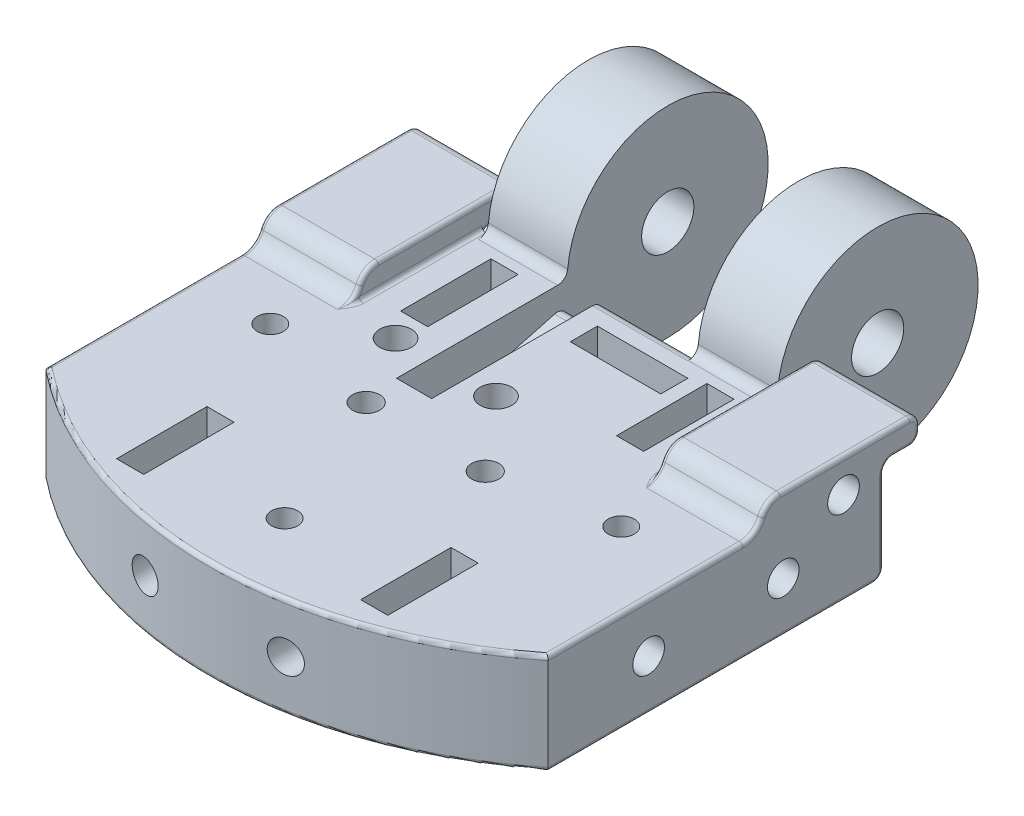
SolidWorks part; units mm, degrees
ref_plane "Front Plane" through (0, 0, 0) normal (0, 0, 1) x (1, 0, 0)
ref_plane "Top Plane" through (0, 0, 0) normal (0, 1, 0) x (1, 0, 0)
ref_plane "Right Plane" through (0, 0, 0) normal (1, 0, 0) x (0, 0, -1)
sketch "Sketch1" plane through (0, 0, 0) normal (0, 1, 0) x (1, 0, 0)
  line L1 (-31.75, 0) -> (31.75, 0)
  line L2 (-31.75, 0) -> (-31.75, -42.418)
  line L4 (31.75, 0) -> (31.75, -42.418)
  arc A0 (-31.75, -42.418) -> (31.75, -42.418) centre (0, -2.7623) ccw
  point P4 (0, 0)
  dimension "D3" = 50.8
  dimension "D1" = 63.5
  dimension "D2" = 42.418
extrude "Boss-Extrude1" add sketch "Sketch1" along normal blind 12.7
ref_plane "Plane1" through (-18.288, 0, 0) normal (-1, 0, 0) x (0, 0, 1)
sketch "Sketch2" plane through (-18.288, 0, 0) normal (-1, 0, 0) x (0, 0, 1)
  line L7 (0, 0) -> (0, 17.5687) construction
  line L9 (0, 0) -> (-12.7, 0)
  line L10 (0, 0) -> (0, 12.7)
  arc A2 (0, 12.7) -> (-12.7, 0) centre (-12.7, 12.7) ccw
  point P2 (-12.7, 0)
  point P3 (0, 12.7)
  dimension "D1" = 25.4
  dimension "D2" = 17.5687
extrude "Boss-Extrude2" add sketch "Sketch2" against normal blind 10.033
mirror "Mirror1" about plane through (0, 0, 0) normal (1, 0, 0) of "Boss-Extrude2"
sketch "Sketch5" plane through (-18.288, 0, 0) normal (-1, 0, 0) x (0, 0, 1)
  circle A0 centre (-12.7, 12.7) radius 3.302
  point P3 (-12.7, 12.7)
  dimension "D1" = 6.604
extrude "Cut-Extrude2" cut sketch "Sketch5" against normal through all
sketch "Sketch13" plane through (0, 12.7, 0) normal (0, 1, 0) x (1, 0, 0)
  line L0 (-31.75, 0) -> (-31.75, -42.418) construction
  line L1 (8.255, 0) -> (-8.255, 0) construction
  circle A0 centre (-12.7, -17.272) radius 2
  circle A1 centre (0, -17.272) radius 2
  dimension "D1" = 4
  dimension "D2" = 19.05
  dimension "D3" = 12.7
  dimension "D4" = 17.272
extrude "Cut-Extrude9" cut sketch "Sketch13" against normal through all
sketch "Sketch17" plane through (0, 12.7, 0) normal (0, 1, 0) x (1, 0, 0)
  line L0 (-31.75, -15.24) -> (-19.05, -15.24)
  line L2 (-31.75, 0) -> (-31.75, 4.572)
  line L3 (-31.75, 4.572) -> (-19.05, 4.572)
  line L4 (-19.05, 0.127) -> (-19.05, 4.572)
  line L7 (-31.75, 0) -> (-31.75, -42.418)
  line L8 (31.75, -42.418) -> (31.75, 0)
  line L9 (31.75, 0) -> (18.288, 0)
  line L10 (18.288, 0) -> (8.255, 0)
  line L11 (8.255, 0) -> (-8.255, 0)
  line L12 (-8.255, 0) -> (-18.288, 0)
  line L13 (-18.288, 0) -> (-31.75, 0)
  line L14 (-31.75, 0) -> (-31.75, -15.24)
  line L22 (-18.288, 0) -> (-31.75, 0) construction
  line L27 (0, 0) -> (0, -53.5623) construction
  line L28 (-19.05, 0.127) -> (-19.05, -15.24)
  line L30 (8.255, 0) -> (-8.255, 0) construction
  line L31 (31.75, -15.24) -> (19.05, -15.24)
  line L32 (19.05, 0.127) -> (19.05, -15.24)
  line L33 (19.05, 0.127) -> (19.05, 4.572)
  line L34 (31.75, 4.572) -> (19.05, 4.572)
  line L35 (31.75, 0) -> (31.75, -15.24)
  line L36 (31.75, 0) -> (31.75, 4.572)
  arc A0 (-31.75, -42.418) -> (31.75, -42.418) centre (0, -2.7623) ccw construction
  arc A1 (-31.75, -42.418) -> (31.75, -42.418) centre (0, -2.7623) ccw
  point P22 (-0.7383, -2.54)
  dimension "D2" = 12.7
  dimension "D3" = 4.572
  dimension "D4" = 15.24
  dimension "D1" = 0
extrude "Boss-Extrude9" add sketch "Sketch17" along normal blind 3.175
ref_plane "Plane2" through (-3.81, 0, 0) normal (1, 0, 0) x (0, 0, -1)
sketch "Sketch19" plane through (-3.81, 0, 0) normal (1, 0, 0) x (0, 0, -1)
  line L1 (-21.59, 4.375) -> (-21.59, 12.7)
  line L2 (-15.24, 15.875) -> (4.572, 15.875) construction
  line L3 (-21.59, 12.7) -> (0, 12.7)
  line L4 (-21.59, 4.375) -> (0, 10.16)
  line L5 (0, 0) -> (0, 12.7) construction
  line L6 (0, 10.16) -> (0, 12.7)
  dimension "D1" = 2.54
  dimension "D2" = 75
  dimension "D3" = 21.59
  dimension "D4" = 3.175
extrude "Cut-Extrude12" cut sketch "Sketch19" against normal blind 4.445
sketch "Sketch23" plane through (0, 0, 0) normal (0, -1, 0) x (-1, 0, 0)
  line L0 (31.75, 0) -> (31.75, -42.418) construction
  line L1 (-31.75, 0) -> (-31.75, -42.418) construction
  line L2 (31.75, -21.209) -> (-31.75, -21.209) construction
  line L3 (23.1652, -1.4218) -> (27.6348, -1.4218)
  line L4 (0, 0) -> (0, -53.5623) construction
  line L5 (-25.4, -5.842) -> (-25.4, -41.402) construction
  line L6 (-21.59, -41.402) -> (-25.4, -41.402) construction
  line L7 (-23.1652, -1.4218) -> (-27.6348, -1.4218)
  arc A0 (23.1652, -1.4218) -> (27.6348, -1.4218) centre (25.4, -5.842) ccw
  arc A1 (-31.75, -42.418) -> (31.75, -42.418) centre (0, -2.7623) ccw construction
  circle A3 centre (21.59, -41.402) radius 4.953
  circle A5 centre (-21.59, -41.402) radius 4.953
  circle A6 centre (0, -22.3203) radius 12.7
  arc A7 (-23.1652, -1.4218) -> (-27.6348, -1.4218) centre (-25.4, -5.842) cw
  point P24 (-25.4, -23.622)
  dimension "D1" = 9.906
  dimension "D4" = 9.906
  dimension "D3" = 35.56
  dimension "D7" = 25.4
  dimension "D8" = 31.242
  dimension "D2" = 50.8
  dimension "D5" = 10.16
  dimension "D6" = 1.016
extrude "Cut-Extrude13" cut sketch "Sketch23" against normal blind 0.0254
sketch "Sketch28" plane through (0, 0, 0) normal (0, -1, 0) x (1, 0, 0)
  line L0 (25.4, 5.842) -> (-25.4, 5.842) construction
  line L1 (31.75, 42.418) -> (31.75, 0) construction
  line L2 (11.9062, 49.7523) -> (-11.9063, 49.7523) construction
  line L3 (11.9062, 49.7523) -> (11.9062, 38.2429) construction
  line L4 (11.9062, 38.2429) -> (-11.9063, 38.2429) construction
  line L5 (-11.9063, 49.7523) -> (-11.9063, 38.2429) construction
  line L6 (11.9062, 49.7523) -> (-11.9063, 38.2429) construction
  line L7 (11.9062, 38.2429) -> (-11.9063, 49.7523) construction
  line L8 (27.94, 35.5283) -> (16.4306, 35.5283) construction
  line L9 (27.94, 35.5283) -> (27.94, 11.7158) construction
  line L10 (27.94, 11.7158) -> (16.4306, 11.7158) construction
  line L11 (16.4306, 35.5283) -> (16.4306, 11.7158) construction
  line L12 (27.94, 35.5283) -> (16.4306, 11.7158) construction
  line L13 (27.94, 11.7158) -> (16.4306, 35.5283) construction
  line L14 (0, 0) -> (0, 53.5623) construction
  line L15 (-27.94, 35.5283) -> (-27.94, 11.7158) construction
  line L16 (-27.94, 35.5283) -> (-16.4306, 35.5283) construction
  line L17 (-16.4306, 35.5283) -> (-16.4306, 11.7158) construction
  line L18 (-27.94, 11.7158) -> (-16.4306, 11.7158) construction
  line L19 (-28.448, 36.0363) -> (-15.9226, 36.0363)
  line L20 (-15.9226, 36.0363) -> (-15.9226, 11.2078)
  line L21 (-28.448, 11.2078) -> (-15.9226, 11.2078)
  line L22 (-28.448, 36.0363) -> (-28.448, 11.2078)
  line L23 (28.448, 36.0363) -> (15.9226, 36.0363)
  line L24 (15.9226, 36.0363) -> (15.9226, 11.2078)
  line L25 (28.448, 11.2078) -> (15.9226, 11.2078)
  line L26 (28.448, 36.0363) -> (28.448, 11.2078)
  line L27 (12.4142, 37.7349) -> (-12.4143, 37.7349)
  line L28 (-12.4143, 50.2603) -> (-12.4143, 37.7349)
  line L29 (12.4142, 50.2603) -> (-12.4143, 50.2603)
  line L30 (12.4142, 50.2603) -> (12.4142, 37.7349)
  line L31 (-27.94, 35.5283) -> (-16.4306, 11.7158) construction
  line L32 (-16.4306, 35.5283) -> (-27.94, 11.7158) construction
  line L33 (28.448, 17.3593) -> (28.448, 29.8847)
  line L34 (-15.9226, 17.3593) -> (-28.448, 17.3593)
  line L35 (-15.9226, 17.3593) -> (-15.9226, 29.8847)
  line L36 (-15.9226, 29.8847) -> (-28.448, 29.8847)
  line L37 (-28.448, 17.3593) -> (-28.448, 29.8847)
  line L38 (-15.9226, 17.3593) -> (-28.448, 29.8847) construction
  line L39 (-15.9226, 29.8847) -> (-28.448, 17.3593) construction
  line L40 (15.9226, 17.3593) -> (28.448, 17.3593)
  line L41 (15.9226, 17.3593) -> (15.9226, 29.8847)
  line L42 (15.9226, 29.8847) -> (28.448, 29.8847)
  line L44 (-6.2627, 50.2603) -> (6.2627, 50.2603)
  line L45 (-6.2627, 50.2603) -> (-6.2627, 37.7349)
  line L46 (-6.2627, 37.7349) -> (6.2627, 37.7349)
  line L47 (6.2627, 50.2603) -> (6.2627, 37.7349)
  line L48 (-6.2627, 50.2603) -> (6.2627, 37.7349) construction
  line L49 (-6.2627, 37.7349) -> (6.2627, 50.2603) construction
  arc A0 (31.75, 42.418) -> (-31.75, 42.418) centre (0, 2.7623) ccw construction
  circle A1 centre (-22.1853, 23.622) radius 4.953
  circle A2 centre (-22.1853, 23.622) radius 1.651
  circle A3 centre (0, 43.9976) radius 4.953
  circle A4 centre (0, 43.9976) radius 1.651
  circle A5 centre (22.1853, 23.622) radius 4.953
  circle A6 centre (22.1853, 23.622) radius 1.651
  point P0 (25.4, 5.842)
  point P1 (-25.4, 5.842)
  point P6 (0, 43.9976)
  point P15 (0, 53.5623)
  point P16 (22.1853, 23.622)
  dimension "D8" = 9.906
  dimension "D9" = 3.302
  dimension "D1" = 11.5094
  dimension "D2" = 23.8125
  dimension "D3" = 3.81
  dimension "D4" = 18.034
  dimension "D5" = 3.81
  dimension "D10" = 50.8
  dimension "D11" = 12.5254
  dimension "D12" = 12.5254
  dimension "D13" = 12.5254
  dimension "D6" = 0.508
  dimension "D7" = 0.508
extrude "Cut-Extrude17" cut sketch "Sketch28" against normal blind 2.032 contours L19 L20 L21 L22 | L29 L28 L27 L30 | L23 L24 L25 L26
extrude "Cut-Extrude18" cut sketch "Sketch28<3>" against normal blind 4.572 contours A1 | A3 | A5
sketch "Sketch28<3>" plane through (0, 0, 0) normal (0, -1, 0) x (1, 0, 0) same geometry as "Sketch28"
extrude "Cut-Extrude26" cut sketch "Sketch28<7>" against normal blind 3.556 contours L36 L37 L34 L35 | L47 L46 L45 L44 | L42 L33 L40 L41
sketch "Sketch28<7>" plane through (0, 0, 0) normal (0, -1, 0) x (1, 0, 0) same geometry as "Sketch28"
extrude "Cut-Extrude19" cut sketch "Sketch28<4>" against normal through all contours A2 | A4 | A6
sketch "Sketch28<4>" plane through (0, 0, 0) normal (0, -1, 0) x (1, 0, 0) same geometry as "Sketch28"
ref_plane "Plane3" through (6.2627, 2.032, 37.7349) normal (-1, 0, 0) x (0, 0, 1)
fillet "Fillet1" radius 1.27 6 edges at (25.4, 12.7, -4.572) (25.4, 12.7, 0) (-25.4, 12.7, -4.572) (-25.4, 12.7, 0) (25.4, 15.875, -4.572) (-25.4, 15.875, -4.572)
sketch "Sketch33" plane through (0, 12.7, 0) normal (0, 1, 0) x (1, 0, 0)
  line L0 (0, -53.5623) -> (0, 0) construction
  line L1 (-17.145, -48.1013) -> (-13.716, -48.1013)
  line L2 (-17.145, -48.1013) -> (-17.145, -36.6713)
  line L3 (-17.145, -36.6713) -> (-13.716, -36.6713)
  line L4 (-13.716, -48.1013) -> (-13.716, -36.6713)
  line L5 (-17.145, -48.1013) -> (-13.716, -36.6713) construction
  line L6 (-17.145, -36.6713) -> (-13.716, -48.1013) construction
  line L7 (13.716, -48.1013) -> (13.716, -36.6713)
  line L8 (17.145, -48.1013) -> (13.716, -48.1013)
  line L9 (17.145, -48.1013) -> (17.145, -36.6713)
  line L10 (17.145, -36.6713) -> (13.716, -36.6713)
  line L11 (-19.05, 0) -> (-8.255, 0) construction
  line L16 (-11.938, -13.97) -> (-15.367, -13.97)
  line L17 (-11.938, -13.97) -> (-11.938, -2.54)
  line L18 (-11.938, -2.54) -> (-15.367, -2.54)
  line L19 (-15.367, -13.97) -> (-15.367, -2.54)
  line L20 (-11.938, -13.97) -> (-15.367, -2.54) construction
  line L21 (-11.938, -2.54) -> (-15.367, -13.97) construction
  line L22 (15.367, -13.97) -> (15.367, -2.54)
  line L23 (11.938, -13.97) -> (15.367, -13.97)
  line L24 (11.938, -13.97) -> (11.938, -2.54)
  line L25 (11.938, -2.54) -> (15.367, -2.54)
  line L26 (8.255, 0) -> (-3.81, 0) construction
  line L27 (-1.27, -6.604) -> (10.16, -6.604)
  line L28 (-1.27, -6.604) -> (-1.27, -3.175)
  line L29 (-1.27, -3.175) -> (10.16, -3.175)
  line L30 (10.16, -6.604) -> (10.16, -3.175)
  line L31 (-1.27, -6.604) -> (10.16, -3.175) construction
  line L32 (-1.27, -3.175) -> (10.16, -6.604) construction
  arc A0 (-31.75, -42.418) -> (31.75, -42.418) centre (0, -2.7623) ccw construction
  point P0 (-15.4305, -42.3863)
  point P15 (-13.6525, -8.255)
  point P24 (-13.6525, 0)
  point P29 (4.445, -4.8895)
  dimension "D1" = 3.429
  dimension "D2" = 11.43
  dimension "D3" = 11.176
  dimension "D4" = 13.716
  dimension "D5" = 2.54
  dimension "D6" = 10.16
  dimension "D7" = 3.175
extrude "Cut-Extrude20" cut sketch "Sketch33" against normal through all
fillet "Fillet2" radius 2.54 2 edges at (25.4, 12.7, 15.24) (-25.4, 12.7, 15.24)
fillet "Fillet3" radius 2.54 2 edges at (25.4, 15.875, 15.24) (-25.4, 15.875, 15.24)
fillet "Fillet4" radius 1.27 3 edges at (-25.019, 0, 0) (0, 0, 0) (25.019, 0, 0)
fillet "Fillet6" radius 1.27 2 edges at (-6.0325, 10.16, 0) (2.2225, 12.7, 0)
fillet "Fillet8" radius 1.27 2 edges at (13.2715, 12.7, 0) (-13.2715, 12.7, 0)
sketch "Sketch34" plane through (-31.75, 0, 0) normal (-1, 0, 0) x (0, 0, 1)
  line L0 (42.418, 0) -> (42.418, 12.7) construction
  line L1 (42.418, 6.35) -> (0, 6.35) construction
  line L2 (0, 0) -> (0, 12.7) construction
  line L3 (0, 6.35) -> (12.7, 6.35) construction
  line L4 (12.7, 6.35) -> (12.7, 2.6535) construction
  line L5 (29.718, 6.35) -> (29.718, 2.6535) construction
  line L6 (12.7, 2.6535) -> (0, 2.6535) construction
  line L7 (29.718, 2.6535) -> (42.418, 2.6535) construction
  circle A0 centre (12.7, 6.35) radius 2
  circle A1 centre (29.718, 6.35) radius 2
  dimension "D1" = 4
  dimension "D3" = 12.7
  dimension "D4" = 3.6965
  dimension "D2" = 2
extrude "Cut-Extrude21" cut sketch "Sketch34" against normal blind 10.16
mirror "Mirror2" about plane through (0, 0, 0) normal (1, 0, 0) of "Cut-Extrude21"
sketch "Sketch35" plane through (31.75, 0, 0) normal (1, 0, 0) x (0, 0, -1)
  line L7 (-42.418, 0) -> (-1.27, 0)
  line L8 (0, 1.27) -> (0, 11.43)
  line L9 (1.27, 12.7) -> (3.302, 12.7)
  line L10 (4.572, 13.97) -> (4.572, 14.605)
  line L11 (3.302, 15.875) -> (-13.0707, 15.875)
  line L12 (-17.78, 12.7) -> (-42.418, 12.7)
  line L13 (-42.418, 12.7) -> (-42.418, 0)
  line L14 (-42.418, 0) -> (-1.27, 0)
  line L15 (0, 1.27) -> (0, 11.43)
  line L16 (1.27, 12.7) -> (3.302, 12.7)
  line L17 (4.572, 13.97) -> (4.572, 14.605)
  line L18 (3.302, 15.875) -> (-13.0707, 15.875)
  line L19 (-17.78, 12.7) -> (-42.418, 12.7)
  line L20 (-42.418, 12.7) -> (-42.418, 0)
  circle A0 centre (-29.718, 6.35) radius 2
  circle A1 centre (-12.7, 6.35) radius 2
  arc A6 (-1.27, 0) -> (0, 1.27) centre (-1.27, 1.27) ccw
  arc A7 (1.27, 12.7) -> (0, 11.43) centre (1.27, 11.43) ccw
  arc A8 (3.302, 12.7) -> (4.572, 13.97) centre (3.302, 13.97) ccw
  arc A9 (4.572, 14.605) -> (3.302, 15.875) centre (3.302, 14.605) ccw
  arc A10 (-13.0707, 15.875) -> (-15.4254, 14.2875) centre (-13.0707, 13.335) ccw
  arc A11 (-17.78, 12.7) -> (-15.4254, 14.2875) centre (-17.78, 15.24) ccw
  arc A12 (-1.27, 0) -> (0, 1.27) centre (-1.27, 1.27) ccw
  arc A13 (1.27, 12.7) -> (0, 11.43) centre (1.27, 11.43) ccw
  arc A14 (3.302, 12.7) -> (4.572, 13.97) centre (3.302, 13.97) ccw
  arc A15 (4.572, 14.605) -> (3.302, 15.875) centre (3.302, 14.605) ccw
  arc A16 (-13.0707, 15.875) -> (-15.4254, 14.2875) centre (-13.0707, 13.335) ccw
  arc A17 (-17.78, 12.7) -> (-15.4254, 14.2875) centre (-17.78, 15.24) ccw
  dimension "D1" = 0
fillet "Fillet9" radius 0.508 26 edges at (0, 0, 53.5623) (0, 12.7, 53.5623) (31.75, 0, 21.844) (31.75, 0.372, 0.372) (31.75, 6.35, 0) (31.75, 12.328, -0.372) (31.75, 12.7, -2.286) (31.75, 13.072, -4.2) (31.75, 14.2875, -4.572) (31.75, 15.503, -4.2) (31.75, 15.875, 4.8844) (31.75, 15.4411, 14.4906) (31.75, 13.1339, 16.3601) (-31.75, 0, 21.844) (-31.75, 0.372, 0.372) (-31.75, 6.35, 0) (-31.75, 12.328, -0.372) (-31.75, 12.7, -2.286) (-31.75, 13.072, -4.2) (-31.75, 14.2875, -4.572) (-31.75, 15.503, -4.2) (-31.75, 15.875, 4.8844) (-31.75, 15.4411, 14.4906) (-31.75, 13.1339, 16.3601) (31.75, 12.7, 30.099) (-31.75, 12.7, 30.099)
fillet "Fillet10" radius 0.508 18 edges at (19.05, 12.328, -0.372) (19.05, 12.7, -2.286) (19.05, 13.072, -4.2) (19.05, 14.2875, -4.572) (19.05, 15.503, -4.2) (19.05, 13.1339, 16.3601) (19.05, 15.4411, 14.4906) (-19.05, 12.328, -0.372) (-19.05, 12.7, -2.286) (-19.05, 13.072, -4.2) (-19.05, 14.2875, -4.572) (-19.05, 15.503, -4.2) (-19.05, 15.875, 4.8844) (-19.05, 13.1339, 16.3601) (19.05, 15.875, 4.8844) (19.05, 12.7, 8.89) (-19.05, 15.4411, 14.4906) (-19.05, 12.7, 8.89)
sketch "Sketch36" plane through (31.75, 0, 0) normal (1, 0, 0) x (0, 0, -1)
  circle A0 centre (-5.08, 11.684) radius 2
  dimension "D1" = 4
  dimension "D2" = 5.08
  dimension "D3" = 11.684
extrude "Cut-Extrude22" cut sketch "Sketch36" against normal blind 7.62 contours A0
sketch "Sketch37" plane through (0, 12.7, 0) normal (0, 1, 0) x (1, 0, 0)
  line L2 (-7.5311, -26.162) -> (7.5311, -26.162) construction
  circle A0 centre (-7.5311, -26.162) radius 1.7145
  circle A2 centre (7.5311, -26.162) radius 1.7145
  point P2 (0, -26.162)
  dimension "D1" = 3.429
  dimension "D2" = 15.0622
  dimension "D3" = 26.162
extrude "Cut-Extrude23" cut sketch "Sketch37" against normal through all
sketch "Sketch38" plane through (0, 0, 0) normal (0, -1, 0) x (1, 0, 0)
  circle A0 centre (-7.5311, 26.162) radius 3.556
  circle A1 centre (7.5311, 26.162) radius 3.556
  dimension "D1" = 7.112
extrude "Cut-Extrude24" cut sketch "Sketch38" against normal blind 6.35
sketch "Sketch39" plane through (0, 0.0254, 0) normal (0, -1, 0) x (1, 0, 0)
  line L2 (-27.6348, 1.4218) -> (-23.1652, 1.4218)
  line L3 (23.1652, 1.4218) -> (27.6348, 1.4218)
  line L5 (17.145, 43.587) -> (17.145, 39.217)
  line L8 (-17.145, 43.587) -> (-17.145, 39.217)
  arc A1 (17.145, 39.217) -> (17.145, 43.587) centre (21.59, 41.402) ccw
  arc A2 (-23.1652, 1.4218) -> (-27.6348, 1.4218) centre (-25.4, 5.842) ccw
  arc A3 (27.6348, 1.4218) -> (23.1652, 1.4218) centre (25.4, 5.842) ccw
  circle A5 centre (-7.5311, 26.162) radius 3.556
  circle A6 centre (7.5311, 26.162) radius 3.556
  circle A7 centre (0, 17.272) radius 2
  arc A9 (-11.0755, 16.1054) -> (-12.3197, 19.2355) centre (-12.7, 17.272) ccw
  arc A10 (-11.0755, 16.1054) -> (-12.3197, 19.2355) centre (0, 22.3203) ccw
  arc A11 (-17.145, 43.587) -> (-17.145, 39.217) centre (-21.59, 41.402) ccw
  dimension "D1" = 50.8
extrude "Boss-Extrude10" [suppressed] add sketch "Sketch39" along normal up to surface (0.0254 mm away) up to face at (0, 0, 4.3373)
fillet "Fillet11" [suppressed] radius 0.762
ref_plane "Plane4" through (0, 0, 42.418) normal (0, 0, 1) x (1, 0, 0)
ref_plane "Plane5" through (0, 0, 53.594) normal (0, 0, 1) x (1, 0, 0)
sketch "Sketch40" plane through (0, 0, 53.594) normal (0, 0, 1) x (1, 0, 0)
  line L0 (0, 0) -> (0, 12.7606) construction
  line L1 (0, 6.3803) -> (31.75, 6.35) construction
  line L2 (31.75, 12.192) -> (31.75, 0.508) construction
  line L3 (0, 6.3803) -> (-31.75, 6.35) construction
  line L4 (-31.75, 12.192) -> (-31.75, 0.508) construction
  circle A0 centre (-8.89, 6.3718) radius 2
  circle A1 centre (8.89, 6.3718) radius 2
  dimension "D1" = 4
  dimension "D2" = 8.89
extrude "Cut-Extrude27" cut sketch "Sketch40" against normal blind 10.16
sketch "Sketch41" plane through (0, 12.7, 0) normal (0, 1, 0) x (1, 0, 0)
  arc A0 (-10.8374, -52.3928) -> (10.89, -52.3813) centre (0, -2.7623) ccw construction
  arc A1 (-31.75, -42.418) -> (31.75, -42.418) centre (0, -2.7623) ccw construction
  arc A2 (-6.9487, -53.0848) -> (6.9487, -53.0848) centre (0, -2.7623) ccw
